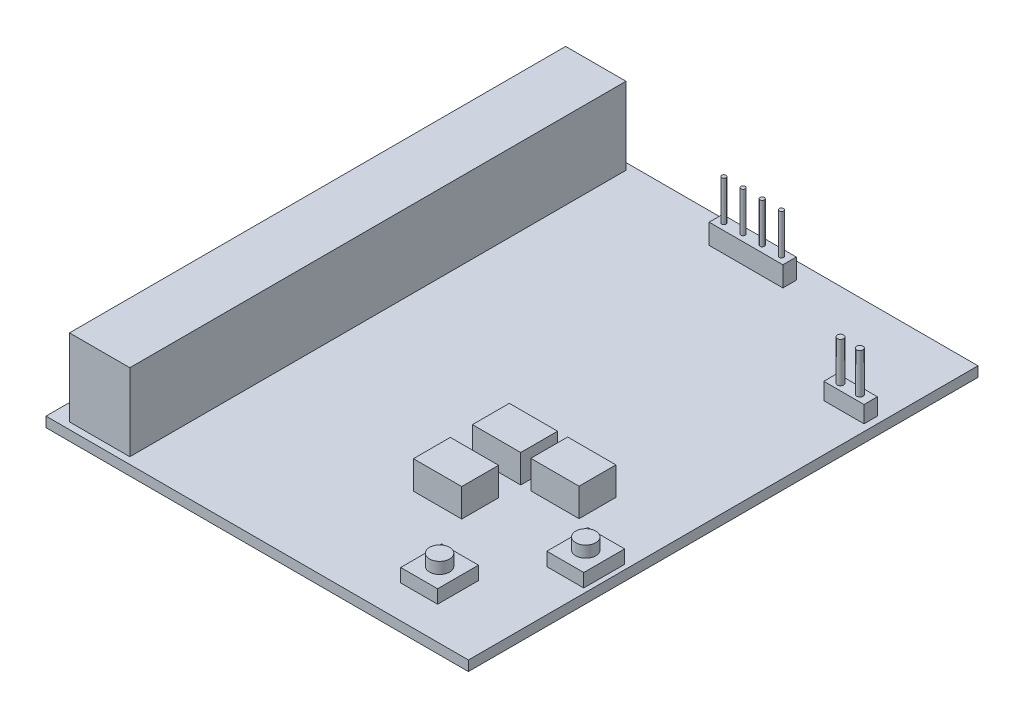
SolidWorks part; units mm, degrees
ref_plane "Front Plane" through (0, 0, 0) normal (0, 0, 1) x (1, 0, 0)
ref_plane "Top Plane" through (0, 0, 0) normal (0, 1, 0) x (1, 0, 0)
ref_plane "Right Plane" through (0, 0, 0) normal (1, 0, 0) x (0, 0, -1)
sketch "Sketch1" plane through (0, 0, 0) normal (0, 1, 0) x (1, 0, 0)
  line L1 (0, 0) -> (63, 0)
  line L2 (0, 0) -> (0, 76)
  line L3 (0, 76) -> (63, 76)
  line L4 (63, 0) -> (63, 76)
  dimension "D1" = 63
  dimension "D2" = 76
extrude "Boss-Extrude1" add sketch "Sketch1" along normal blind 1.5
sketch "Sketch2" plane through (0, 1.5, 0) normal (0, 1, 0) x (1, 0, 0)
  line L0 (63, 76) -> (0, 76) construction
  line L1 (2.5, 75) -> (11.5, 75)
  line L2 (2.5, 75) -> (2.5, 1)
  line L3 (2.5, 1) -> (11.5, 1)
  line L4 (11.5, 75) -> (11.5, 1)
  line L5 (0, 76) -> (0, 0) construction
  dimension "D1" = 74
  dimension "D2" = 1
  dimension "D3" = 2.5
  dimension "D4" = 9
extrude "Boss-Extrude2" add sketch "Sketch2" along normal blind 11.5
sketch "Sketch3" plane through (0, 0, 0) normal (0, -1, 0) x (1, 0, 0)
  line L0 (0, -76) -> (0, 0) construction
  line L1 (9, -15) -> (16, -15)
  line L2 (9, -15) -> (9, -23)
  line L3 (9, -23) -> (16, -23)
  line L4 (16, -15) -> (16, -23)
  line L5 (9, -34) -> (16, -34)
  line L6 (9, -34) -> (9, -42)
  line L7 (9, -42) -> (16, -42)
  line L8 (16, -34) -> (16, -42)
  line L9 (9, -56) -> (16, -56)
  line L10 (9, -56) -> (9, -64)
  line L11 (9, -64) -> (16, -64)
  line L12 (16, -56) -> (16, -64)
  line L13 (63, -76) -> (0, -76) construction
  dimension "D1" = 8
  dimension "D2" = 8
  dimension "D3" = 8
  dimension "D4" = 7
  dimension "D5" = 7
  dimension "D6" = 7
  dimension "D7" = 9
  dimension "D8" = 9
  dimension "D9" = 9
  dimension "D10" = 12
  dimension "D11" = 34
  dimension "D12" = 53
extrude "Boss-Extrude3" add sketch "Sketch3" along normal blind 3.5
sketch "Sketch4" plane through (0, 1.5, 0) normal (0, 1, 0) x (1, 0, 0)
  line L0 (63, 0) -> (63, 76) construction
  line L1 (27.4, 73.5) -> (38.4, 73.5)
  line L2 (27.4, 73.5) -> (27.4, 71.5)
  line L3 (27.4, 71.5) -> (38.4, 71.5)
  line L4 (38.4, 73.5) -> (38.4, 71.5)
  line L5 (63, 76) -> (0, 76) construction
  dimension "D1" = 11
  dimension "D2" = 2
  dimension "D3" = 24.6
  dimension "D4" = 2.5
extrude "Boss-Extrude4" add sketch "Sketch4" along normal blind 3
sketch "Sketch5" plane through (0, 4.5, 0) normal (0, 1, 0) x (1, 0, 0)
  line L0 (27.4, 73.5) -> (27.4, 71.5) construction
  line L1 (38.4, 73.5) -> (27.4, 73.5) construction
  circle A0 centre (28.6, 72.5) radius 0.325
  circle A1 centre (31.46, 72.5) radius 0.325
  circle A2 centre (34.32, 72.5) radius 0.325
  circle A3 centre (37.18, 72.5) radius 0.325
  dimension "D1" = 0.65
  dimension "D2" = 1.2
  dimension "D4" = 1
  dimension "D3" = 4
extrude "Boss-Extrude5" add sketch "Sketch5" along normal blind 6
sketch "Sketch6" plane through (0, 1.5, 0) normal (0, 1, 0) x (1, 0, 0)
  line L0 (63, 0) -> (63, 76) construction
  line L1 (56, 62) -> (62, 62)
  line L2 (56, 62) -> (56, 60)
  line L3 (56, 60) -> (62, 60)
  line L4 (62, 62) -> (62, 60)
  line L5 (63, 76) -> (0, 76) construction
  dimension "D1" = 6
  dimension "D2" = 2
  dimension "D3" = 1
  dimension "D4" = 14
extrude "Boss-Extrude6" add sketch "Sketch6" along normal blind 2.5
sketch "Sketch7" plane through (0, 4, 0) normal (0, 1, 0) x (1, 0, 0)
  line L0 (56, 62) -> (56, 60) construction
  circle A0 centre (57.5, 60.989) radius 0.4731
  circle A1 centre (60.4, 60.989) radius 0.4731
  dimension "D1" = 1.5
  dimension "D2" = 2
extrude "Boss-Extrude7" add sketch "Sketch7" along normal blind 6
sketch "Sketch8" plane through (0, 1.5, 0) normal (0, 1, 0) x (1, 0, 0)
  line L0 (63, 0) -> (63, 76) construction
  line L1 (37.1, 32) -> (44.3, 32)
  line L2 (37.1, 32) -> (37.1, 26.5)
  line L3 (37.1, 26.5) -> (44.3, 26.5)
  line L4 (44.3, 32) -> (44.3, 26.5)
  line L5 (45.8, 32) -> (53, 32)
  line L6 (45.8, 32) -> (45.8, 26.5)
  line L7 (45.8, 26.5) -> (53, 26.5)
  line L8 (53, 32) -> (53, 26.5)
  line L9 (37.1, 23.2) -> (44.3, 23.2)
  line L10 (37.1, 23.2) -> (37.1, 17.7)
  line L11 (37.1, 17.7) -> (44.3, 17.7)
  line L12 (44.3, 23.2) -> (44.3, 17.7)
  line L13 (0, 0) -> (63, 0) construction
  dimension "D1" = 7.2
  dimension "D2" = 7.2
  dimension "D3" = 7.2
  dimension "D4" = 5.5
  dimension "D5" = 5.5
  dimension "D6" = 5.5
  dimension "D7" = 10
  dimension "D8" = 18.7
  dimension "D9" = 18.7
  dimension "D10" = 17.7
  dimension "D11" = 26.5
  dimension "D12" = 26.5
extrude "Boss-Extrude8" add sketch "Sketch8" along normal blind 4.2
sketch "Sketch9" plane through (0, 1.5, 0) normal (0, 1, 0) x (1, 0, 0)
  line L0 (63, 0) -> (63, 76) construction
  line L1 (56.8, 24) -> (62.3, 24)
  line L2 (56.8, 24) -> (56.8, 17.9)
  line L3 (56.8, 17.9) -> (62.3, 17.9)
  line L4 (62.3, 24) -> (62.3, 17.9)
  line L5 (0, 0) -> (63, 0) construction
  dimension "D1" = 0.7
  dimension "D2" = 6.1
  dimension "D3" = 17.9
  dimension "D4" = 5.5
extrude "Boss-Extrude9" add sketch "Sketch9" along normal blind 2
sketch "Sketch10" plane through (0, 3.5, 0) normal (0, 1, 0) x (1, 0, 0)
  line L0 (62.3, 17.9) -> (62.3, 24) construction
  line L1 (62.3, 24) -> (56.8, 24) construction
  circle A0 centre (59.55, 20.95) radius 1.5
  dimension "D1" = 3
  dimension "D2" = 2.75
  dimension "D3" = 3.05
extrude "Boss-Extrude10" add sketch "Sketch10" along normal blind 1.7
sketch "Sketch11" plane through (0, 1.5, 0) normal (0, 1, 0) x (1, 0, 0)
  line L0 (63, 0) -> (63, 76) construction
  line L1 (48, 11) -> (53.5, 11)
  line L2 (48, 11) -> (48, 4.9)
  line L3 (48, 4.9) -> (53.5, 4.9)
  line L4 (53.5, 11) -> (53.5, 4.9)
  line L5 (0, 0) -> (63, 0) construction
  line L6 (56.8, 17.9) -> (62.3, 17.9) construction
  line L7 (62.3, 17.9) -> (62.3, 24) construction
  dimension "D1" = 9.5
  dimension "D2" = 4.9
extrude "Boss-Extrude11" add sketch "Sketch11" along normal blind 2
sketch "Sketch12" plane through (0, 3.5, 0) normal (0, 1, 0) x (1, 0, 0)
  line L0 (53.5, 4.9) -> (53.5, 11) construction
  line L1 (53.5, 11) -> (48, 11) construction
  circle A0 centre (50.75, 7.95) radius 1.5
  circle A1 centre (59.55, 20.95) radius 1.5 construction
  point P6 (50.75, 11)
  dimension "D1" = 2.75
  dimension "D2" = 3.05
extrude "Boss-Extrude12" add sketch "Sketch12" along normal blind 1.7 contours A0
